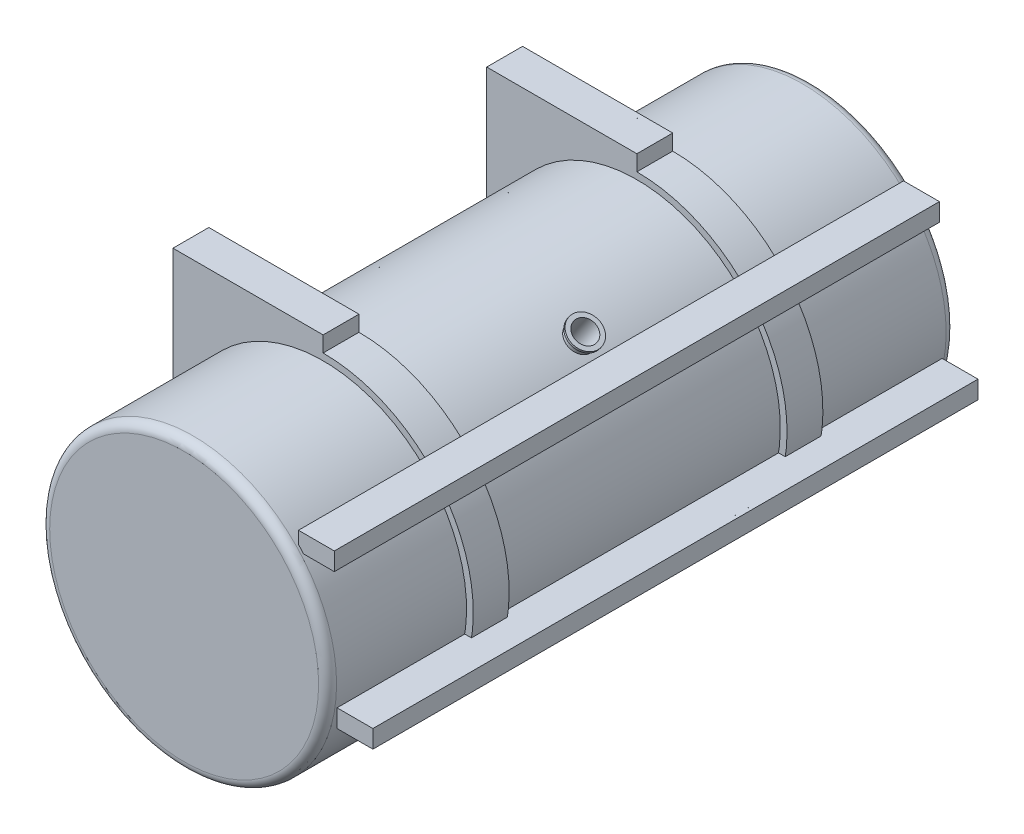
SolidWorks part; units mm, degrees
ref_plane "Front Plane" through (0, 0, 0) normal (0, 0, 1) x (1, 0, 0)
ref_plane "Top Plane" through (0, 0, 0) normal (0, 1, 0) x (1, 0, 0)
ref_plane "Right Plane" through (0, 0, 0) normal (1, 0, 0) x (0, 0, -1)
sketch "Sketch1" plane through (0, 0, 0) normal (0, 0, 1) x (1, 0, 0)
  circle A0 centre (0, 0) radius 320
  circle A1 centre (0, 0) radius 310
  dimension "D1" = 640
  dimension "D2" = 10
extrude "Boss-Extrude1" add sketch "Sketch1" along normal mid plane 1400
sketch "Sketch2" plane through (0, 0, 700) normal (0, 0, 1) x (1, 0, 0)
  circle A0 centre (0, 0) radius 320
extrude "Boss-Extrude2" add sketch "Sketch2" against normal blind 10
fillet "Fillet1" radius 20 2 edges at (320, 0, 700) (310, 0, 690)
mirror "Mirror1" about plane through (0, 0, 0) normal (0, 0, 1) of "Boss-Extrude2"
fillet "Fillet2" radius 20 2 edges at (320, 0, -700) (-310, 0, -690)
sketch "Sketch3" plane through (0, 0, 0) normal (0, 0, 1) x (1, 0, 0)
  line L0 (120, 296.6479) -> (120, 411.4566)
  line L1 (230, 250) -> (310, 250)
  line L2 (230, 250) -> (230, 210)
  line L3 (230, 210) -> (310, 210)
  line L4 (310, 250) -> (310, 210)
  line L5 (320, 0) -> (320, 184.3985)
  line L7 (316.0696, -90) -> (396.0696, -90)
  line L8 (316.0696, -90) -> (316.0696, -50)
  line L9 (316.0696, -50) -> (396.0696, -50)
  line L10 (396.0696, -90) -> (396.0696, -50)
  circle A0 centre (0, 0) radius 320 construction
  dimension "D7" = 80
  dimension "D1" = 200
  dimension "D2" = 80
  dimension "D3" = 40
  dimension "D4" = 210
  dimension "D5" = 296.6479
  dimension "D6" = 10
  dimension "D8" = 40
  dimension "D9" = 50
extrude "Boss-Extrude3" add sketch "Sketch3" along normal mid plane 1350 contours L4 L1 L2 L3 | L7 L10 L9 L8 region at (270, 230, 0) region at (356.0696, -70, 0)
ref_plane "Plane1" through (0, 0, 350) normal (0, 0, 1) x (1, 0, 0)
sketch "Sketch4" plane through (0, 0, 350) normal (0, 0, 1) x (1, 0, 0)
  line L0 (-335, 0) -> (-335, 370)
  line L1 (241.4539, 210) -> (310, 210) construction
  line L2 (280, 183.9157) -> (300, 210)
  line L3 (261.0077, 210) -> (300, 210)
  line L4 (-335, 370) -> (0, 370)
  line L5 (0, 370) -> (0, 335)
  line L6 (322.6841, -90) -> (386.0696, -90)
  line L7 (316.0696, -90) -> (396.0696, -90) construction
  line L8 (386.0696, -90) -> (299.5413, -150)
  circle A0 centre (0, 0) radius 320
  arc A1 (261.0077, 210) -> (0, 335) centre (0, 0) ccw
  circle A2 centre (0, 0) radius 320 construction
  arc A3 (-335, 0) -> (299.5413, -150) centre (0, 0) ccw
  arc A4 (322.6841, -90) -> (280, 183.9157) centre (0, 0) ccw
  dimension "D1" = 15
  dimension "D2" = 10
  dimension "D3" = 30
  dimension "D4" = 370
  dimension "D5" = 10
  dimension "D6" = 60
extrude "Boss-Extrude4" add sketch "Sketch4" along normal mid plane 80
sketch "Sketch7" plane through (0, 0, 350) normal (0, 0, 1) x (1, 0, 0)
  line L0 (-335, 360) -> (-10, 360)
  line L1 (-335, 370) -> (-335, 0) construction
  line L2 (-10, 360) -> (-10, 334.8507)
  line L3 (-335, 360) -> (-335, 0)
  line L4 (0, 370) -> (-335, 370) construction
  line L5 (0, 335) -> (0, 370) construction
  arc A0 (-10, 334.8507) -> (-335, 0) centre (0, 0) ccw
  arc A1 (230, 243.5672) -> (0, 335) centre (0, 0) ccw construction
  dimension "D1" = 10
  dimension "D2" = 10
extrude "Cut-Extrude1" cut sketch "Sketch7" against normal mid plane 60
mirror "Mirror2" about plane through (0, 0, 0) normal (0, 0, 1) of "Cut-Extrude1", "Boss-Extrude4"
sketch "Sketch5" plane through (0, 0, 0) normal (0, 0, 1) x (1, 0, 0)
  line L0 (0, 0) -> (195.016, 278.5117) construction
  line L1 (0, 0) -> (0, 126.3718) construction
  line L2 (132.2923, 232.5192) -> (174.5372, 292.8511)
  line L3 (174.5372, 292.8511) -> (195.016, 278.5117)
  line L4 (132.2923, 232.5192) -> (152.7711, 218.1798)
  line L5 (174.5372, 292.8511) -> (170.4414, 295.719)
  line L6 (128.1966, 235.3871) -> (167.5735, 291.6232)
  line L7 (128.1966, 235.3871) -> (132.2923, 232.5192)
  line L8 (195.016, 278.5117) -> (152.7711, 218.1798)
  line L9 (170.4414, 295.719) -> (166.3457, 298.5869)
  line L10 (163.4778, 294.4911) -> (166.3457, 298.5869)
  line L11 (167.5735, 291.6232) -> (163.4778, 294.4911)
  dimension "D1" = 35
  dimension "D2" = 25
  dimension "D3" = 340
  dimension "D4" = 5
  dimension "D5" = 5
  dimension "D6" = 5
revolve "Cut-Revolve1" cut sketch "Sketch5" angle 360 about L0 region at (163.6542, 255.5154, 0)
revolve "Revolve1" add sketch "Sketch5<3>" angle 360 about L0 region at (152.3581, 266.0889, 0)
sketch "Sketch5<3>" plane through (0, 0, 0) normal (0, 0, 1) x (1, 0, 0) same geometry as "Sketch5"
